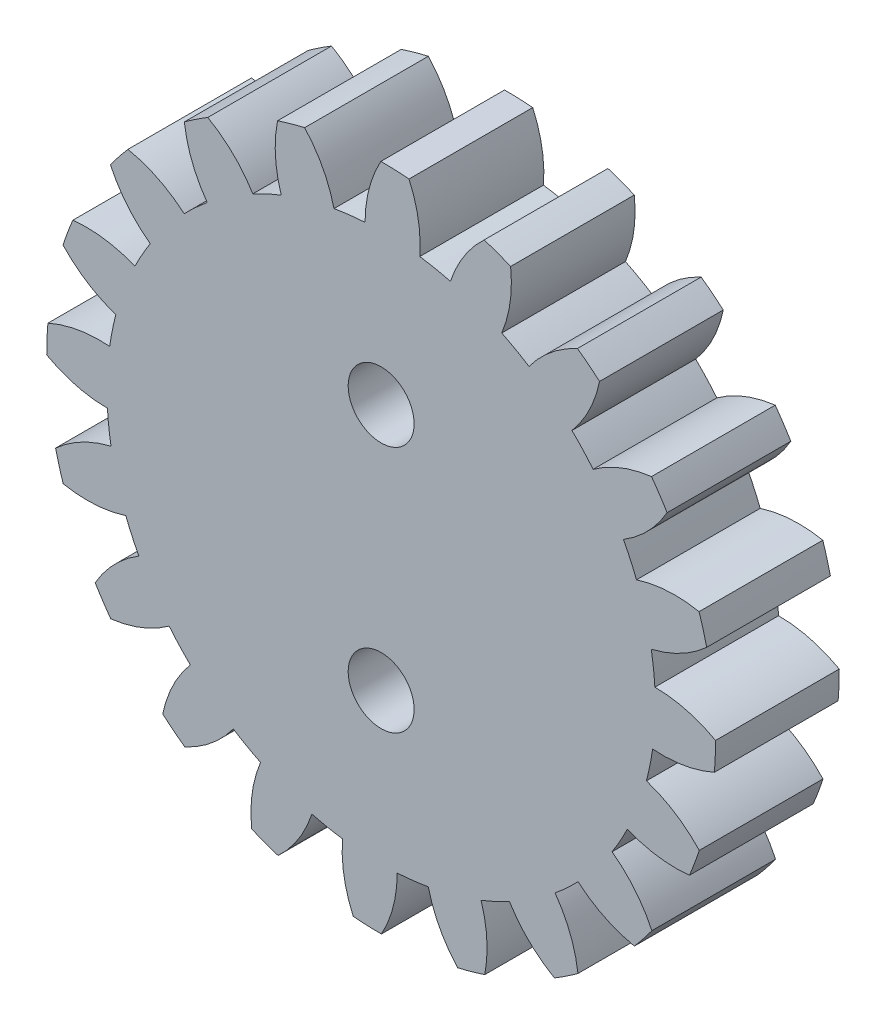
SolidWorks part; units mm, degrees
ref_plane "前视基准面" through (0, 0, 0) normal (0, 0, 1) x (1, 0, 0)
ref_plane "上视基准面" through (0, 0, 0) normal (0, 1, 0) x (1, 0, 0)
ref_plane "右视基准面" through (0, 0, 0) normal (1, 0, 0) x (0, 0, -1)
sketch "草图4" plane through (0, 0, 0) normal (0, 0, 1) x (1, 0, 0)
  arc A0 (6.6376, 0.3903) -> (6.5499, 1.1439) centre (0, 0) ccw
  arc A1 (8.3587, -0.1477) -> (6.6376, 0.3903) centre (6.6319, -2.6497) ccw
  arc A2 (8.3424, -0.5418) -> (8.3587, -0.1477) centre (0, 0) ccw
  arc A3 (6.5828, -0.9361) -> (8.3424, -0.5418) centre (6.8278, 2.094) ccw
  arc A4 (6.4333, -1.6799) -> (6.5828, -0.9361) centre (0, 0) ccw
  arc A5 (7.9039, -2.7235) -> (6.4333, -1.6799) centre (5.4885, -4.5694) ccw
  arc A6 (7.7667, -3.0933) -> (7.9039, -2.7235) centre (0, 0) ccw
  arc A7 (5.9714, -2.9245) -> (7.7667, -3.0933) centre (7.1407, -0.1184) ccw
  arc A8 (5.5993, -3.5857) -> (5.9714, -2.9245) centre (0, 0) ccw
  arc A9 (6.6755, -5.0326) -> (5.5993, -3.5857) centre (3.8079, -6.0418) ccw
  arc A10 (6.4307, -5.3419) -> (6.6755, -5.0326) centre (0, 0) ccw
  arc A11 (4.7754, -4.6266) -> (6.4307, -5.3419) centre (6.7546, -2.3192) ccw
  arc A12 (4.2172, -5.1405) -> (4.7754, -4.6266) centre (0, 0) ccw
  arc A13 (4.7936, -6.8492) -> (4.2172, -5.1405) centre (1.7545, -6.9228) ccw
  arc A14 (4.4652, -7.0676) -> (4.7936, -6.8492) centre (0, 0) ccw
  arc A15 (3.1119, -5.8759) -> (4.4652, -7.0676) centre (5.7073, -4.293) ccw
  arc A16 (2.4223, -6.1921) -> (3.1119, -5.8759) centre (0, 0) ccw
  arc A17 (2.4425, -7.9952) -> (2.4223, -6.1921) centre (-0.4706, -7.1261) ccw
  arc A18 (2.0626, -8.1015) -> (2.4425, -7.9952) centre (0, 0) ccw
  arc A19 (1.1439, -6.5499) -> (2.0626, -8.1015) centre (4.1014, -5.8465) ccw
  arc A20 (0.3903, -6.6376) -> (1.1439, -6.5499) centre (0, 0) ccw
  arc A21 (-0.1477, -8.3587) -> (0.3903, -6.6376) centre (-2.6497, -6.6319) ccw
  arc A22 (-0.5418, -8.3424) -> (-0.1477, -8.3587) centre (0, 0) ccw
  arc A23 (-0.9361, -6.5828) -> (-0.5418, -8.3424) centre (2.094, -6.8278) ccw
  arc A24 (-1.6799, -6.4333) -> (-0.9361, -6.5828) centre (0, 0) ccw
  arc A25 (-2.7235, -7.9039) -> (-1.6799, -6.4333) centre (-4.5694, -5.4885) ccw
  arc A26 (-3.0933, -7.7667) -> (-2.7235, -7.9039) centre (0, 0) ccw
  arc A27 (-2.9245, -5.9714) -> (-3.0933, -7.7667) centre (-0.1184, -7.1407) ccw
  arc A28 (-3.5857, -5.5993) -> (-2.9245, -5.9714) centre (0, 0) ccw
  arc A29 (-5.0326, -6.6755) -> (-3.5857, -5.5993) centre (-6.0418, -3.8079) ccw
  arc A30 (-5.3419, -6.4307) -> (-5.0326, -6.6755) centre (0, 0) ccw
  arc A31 (-4.6266, -4.7754) -> (-5.3419, -6.4307) centre (-2.3192, -6.7546) ccw
  arc A32 (-5.1405, -4.2172) -> (-4.6266, -4.7754) centre (0, 0) ccw
  arc A33 (-6.8492, -4.7936) -> (-5.1405, -4.2172) centre (-6.9228, -1.7545) ccw
  arc A34 (-7.0676, -4.4652) -> (-6.8492, -4.7936) centre (0, 0) ccw
  arc A35 (-5.8759, -3.1119) -> (-7.0676, -4.4652) centre (-4.293, -5.7073) ccw
  arc A36 (-6.1921, -2.4223) -> (-5.8759, -3.1119) centre (0, 0) ccw
  arc A37 (-7.9952, -2.4425) -> (-6.1921, -2.4223) centre (-7.1261, 0.4706) ccw
  arc A38 (-8.1015, -2.0626) -> (-7.9952, -2.4425) centre (0, 0) ccw
  arc A39 (-6.5499, -1.1439) -> (-8.1015, -2.0626) centre (-5.8465, -4.1014) ccw
  arc A40 (-6.6376, -0.3903) -> (-6.5499, -1.1439) centre (0, 0) ccw
  arc A41 (-8.3587, 0.1477) -> (-6.6376, -0.3903) centre (-6.6319, 2.6497) ccw
  arc A42 (-8.3424, 0.5418) -> (-8.3587, 0.1477) centre (0, 0) ccw
  arc A43 (-6.5828, 0.9361) -> (-8.3424, 0.5418) centre (-6.8278, -2.094) ccw
  arc A44 (-6.4333, 1.6799) -> (-6.5828, 0.9361) centre (0, 0) ccw
  arc A45 (-7.9039, 2.7235) -> (-6.4333, 1.6799) centre (-5.4885, 4.5694) ccw
  arc A46 (-7.7667, 3.0933) -> (-7.9039, 2.7235) centre (0, 0) ccw
  arc A47 (-5.9714, 2.9245) -> (-7.7667, 3.0933) centre (-7.1407, 0.1184) ccw
  arc A48 (-5.5993, 3.5857) -> (-5.9714, 2.9245) centre (0, 0) ccw
  arc A49 (-6.6755, 5.0326) -> (-5.5993, 3.5857) centre (-3.8079, 6.0418) ccw
  arc A50 (-6.4307, 5.3419) -> (-6.6755, 5.0326) centre (0, 0) ccw
  arc A51 (-4.7754, 4.6266) -> (-6.4307, 5.3419) centre (-6.7546, 2.3192) ccw
  arc A52 (-4.2172, 5.1405) -> (-4.7754, 4.6266) centre (0, 0) ccw
  arc A53 (-4.7936, 6.8492) -> (-4.2172, 5.1405) centre (-1.7545, 6.9228) ccw
  arc A54 (-4.4652, 7.0676) -> (-4.7936, 6.8492) centre (0, 0) ccw
  arc A55 (-3.1119, 5.8759) -> (-4.4652, 7.0676) centre (-5.7073, 4.293) ccw
  arc A56 (-2.4223, 6.1921) -> (-3.1119, 5.8759) centre (0, 0) ccw
  arc A57 (-2.4425, 7.9952) -> (-2.4223, 6.1921) centre (0.4706, 7.1261) ccw
  arc A58 (-2.0626, 8.1015) -> (-2.4425, 7.9952) centre (0, 0) ccw
  arc A59 (-1.1439, 6.5499) -> (-2.0626, 8.1015) centre (-4.1014, 5.8465) ccw
  arc A60 (-0.3903, 6.6376) -> (-1.1439, 6.5499) centre (0, 0) ccw
  arc A61 (0.1477, 8.3587) -> (-0.3903, 6.6376) centre (2.6497, 6.6319) ccw
  arc A62 (0.5418, 8.3424) -> (0.1477, 8.3587) centre (0, 0) ccw
  arc A63 (0.9361, 6.5828) -> (0.5418, 8.3424) centre (-2.094, 6.8278) ccw
  arc A64 (1.6799, 6.4333) -> (0.9361, 6.5828) centre (0, 0) ccw
  arc A65 (2.7235, 7.9039) -> (1.6799, 6.4333) centre (4.5694, 5.4885) ccw
  arc A66 (3.0933, 7.7667) -> (2.7235, 7.9039) centre (0, 0) ccw
  arc A67 (2.9245, 5.9714) -> (3.0933, 7.7667) centre (0.1184, 7.1407) ccw
  arc A68 (3.5857, 5.5993) -> (2.9245, 5.9714) centre (0, 0) ccw
  arc A69 (5.0326, 6.6755) -> (3.5857, 5.5993) centre (6.0418, 3.8079) ccw
  arc A70 (5.3419, 6.4307) -> (5.0326, 6.6755) centre (0, 0) ccw
  arc A71 (4.6266, 4.7754) -> (5.3419, 6.4307) centre (2.3192, 6.7546) ccw
  arc A72 (5.1405, 4.2172) -> (4.6266, 4.7754) centre (0, 0) ccw
  arc A73 (6.8492, 4.7936) -> (5.1405, 4.2172) centre (6.9228, 1.7545) ccw
  arc A74 (7.0676, 4.4652) -> (6.8492, 4.7936) centre (0, 0) ccw
  arc A75 (5.8759, 3.1119) -> (7.0676, 4.4652) centre (4.293, 5.7073) ccw
  arc A76 (6.1921, 2.4223) -> (5.8759, 3.1119) centre (0, 0) ccw
  arc A77 (7.9952, 2.4425) -> (6.1921, 2.4223) centre (7.1261, -0.4706) ccw
  arc A78 (8.1015, 2.0626) -> (7.9952, 2.4425) centre (0, 0) ccw
  arc A79 (6.5499, 1.1439) -> (8.1015, 2.0626) centre (5.8465, 4.1014) ccw
  circle A81 centre (0, 0) radius 8.1093
extrude "凸台-拉伸4" add sketch "草图4" along normal blind 3 contours A79 A81 A77 A76 A75 A73 A72 A71 A69 A68 A67 A65 A64 A63 A61 A60 A59 A57 A56 A55 A53 A52 A51 A49 A48 A47 A45 A44 A43 A41 A40 A39 A37 A36 A35 A33 A32 A31 A29 region at (0, 0, 0)
sketch "草图5" plane through (0, 0, 0) normal (0, 0, -1) x (-1, 0, 0)
  line L0 (0, 0) -> (3.9024, 0) construction
  line L1 (0, 0) -> (0, 9.6034) construction
  circle A0 centre (0, 3) radius 0.8
  circle A1 centre (0, -3) radius 0.8
  dimension "D1" = 3
  dimension "D2" = 1.6
extrude "切除-拉伸1" cut sketch "草图5" against normal up to next
